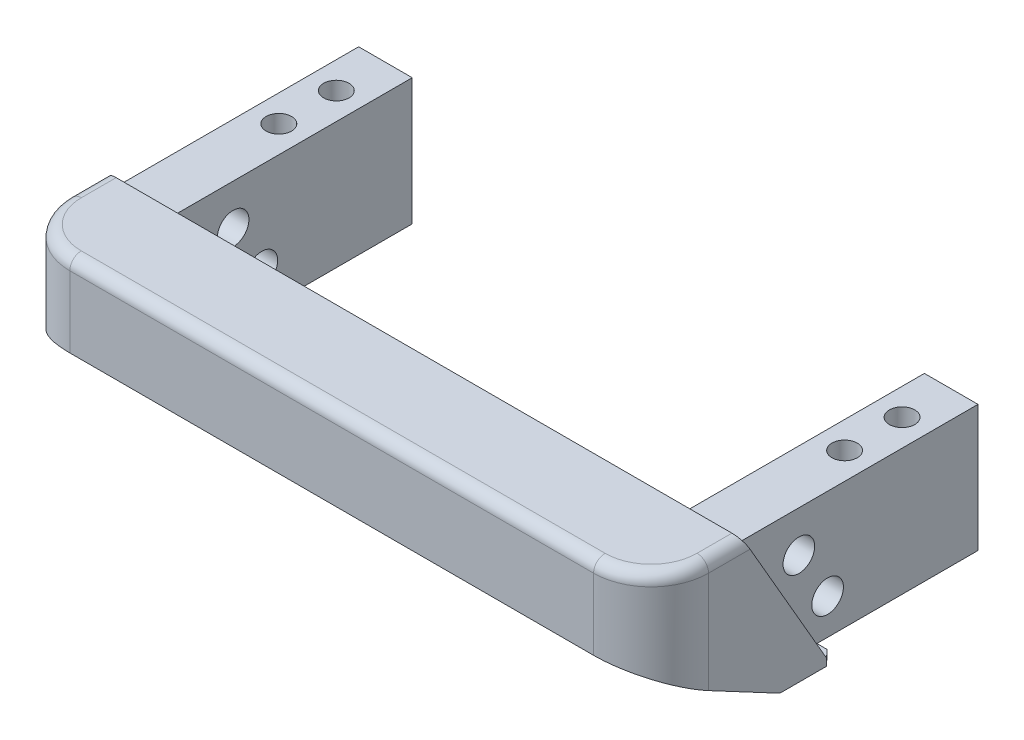
SolidWorks part; units mm, degrees
ref_plane "Front Plane" through (0, 0, 0) normal (0, 0, 1) x (1, 0, 0)
ref_plane "Top Plane" through (0, 0, 0) normal (0, 1, 0) x (1, 0, 0)
ref_plane "Right Plane" through (0, 0, 0) normal (1, 0, 0) x (0, 0, -1)
sketch "Sketch1" plane through (0, 0, 0) normal (1, 0, 0) x (0, 0, -1)
  line L0 (0, 0) -> (0, 50.8)
  line L5 (0, 50.8) -> (29.3294, 0)
  line L6 (29.3294, 0) -> (0, 0)
  dimension "D1" = 60
  dimension "D2" = 50.8
extrude "Boss-Extrude1" add sketch "Sketch1" along normal blind 222.25
sketch "Sketch3" plane through (0, 0, 0) normal (0, 0, 1) x (1, 0, 0)
  line L0 (196.85, 50.8) -> (196.85, 0) construction
  line L1 (218.875, 47.425) -> (200.225, 47.425)
  line L2 (218.875, 47.425) -> (218.875, 3.375)
  line L3 (218.875, 3.375) -> (200.225, 3.375)
  line L4 (200.225, 47.425) -> (200.225, 3.375)
  line L5 (222.25, 50.8) -> (222.25, 0) construction
  line L6 (222.25, 50.8) -> (0, 50.8) construction
  line L7 (222.25, 0) -> (0, 0) construction
  dimension "D1" = 3.375
  dimension "D2" = 3.375
  dimension "D3" = 3.375
  dimension "D4" = 18.65
  dimension "D5" = 25.4
extrude "Boss-Extrude3" add sketch "Sketch3" against normal blind 85 contours L1 L4 L3 L2 region at (209.55, 25.4, 0)
sketch "Sketch15" plane through (0, 47.425, 0) normal (0, 1, 0) x (1, 0, 0)
  circle A0 centre (209.55, 67.9086) radius 4.4196
  circle A1 centre (209.55, 47.9086) radius 4.4196
  dimension "D1" = 8.8392
  dimension "D2" = 8.8392
extrude "Cut-Extrude6" cut sketch "Sketch15" against normal blind 15
sketch "Sketch16" plane through (200.225, 0, 0) normal (-1, 0, 0) x (0, 0, 1)
  circle A0 centre (-22.6727, 33.1173) radius 5.5
  circle A1 centre (-32.6727, 15.7967) radius 5.5
  dimension "D1" = 11
  dimension "D2" = 11
extrude "Cut-Extrude7" cut sketch "Sketch16" against normal through all
ref_plane "Plane1" through (111.125, 0, 0) normal (-1, 0, 0) x (0, 0, 1)
mirror "Mirror1" about plane through (111.125, 0, 0) normal (-1, 0, 0) of "Cut-Extrude7", "Boss-Extrude3", "Cut-Extrude6"
sketch "Sketch4" plane through (222.25, 0, 0) normal (1, 0, 0) x (0, 0, -1)
  line L0 (-5, 50.8) -> (-26.1464, 36.606)
  line L3 (0, 0) -> (0, 50.8)
  line L4 (0, 50.8) -> (-5, 50.8)
  line L5 (0, 0) -> (-5, 0)
  line L6 (-15, 0) -> (-5, 0)
  line L7 (-5, 50.8) -> (-5, 0) construction
  arc A0 (-15, 0) -> (-26.1464, 36.606) centre (-15, 20) cw
  dimension "D2" = 20
  dimension "D1" = 10
  dimension "D3" = 5
extrude "Boss-Extrude4" [suppressed] add sketch "Sketch4" against normal up to surface (222.25 mm away) up to face at (0, 16.9333, -9.7765)
sketch "Sketch7" plane through (222.25, 0, 0) normal (1, 0, 0) x (0, 0, -1)
  line L0 (0, 50.8) -> (-32.1286, 50.8)
  line L2 (-32.1286, 22.0436) -> (9.3294, 0)
  line L3 (0, 0) -> (29.3294, 0) construction
  line L4 (9.3294, 0) -> (29.3294, 0)
  line L5 (29.3294, 0) -> (0, 50.8)
  line L8 (-32.1286, 50.8) -> (-32.1286, 22.0436)
  dimension "D1" = 32
  dimension "D2" = 20
  dimension "D3" = 32.1286
extrude "Boss-Extrude5" add sketch "Sketch7" against normal up to surface (222.25 mm away) up to face at (0, 16.9333, -9.7765)
sketch "Sketch8" plane through (222.25, 0, 0) normal (1, 0, 0) x (0, 0, -1)
  line L0 (-32.1286, 22.0436) -> (9.3294, 0) construction
  line L1 (0, 4.9605) -> (9.3294, 0)
  line L2 (0, 4.9605) -> (0, 0)
  line L3 (0, 0) -> (9.3294, 0)
extrude "Cut-Extrude3" cut sketch "Sketch8" against normal up to surface (222.25 mm away) up to face at (0, 21.434, 5.8213)
sketch "Sketch9" plane through (222.25, 0, 0) normal (1, 0, 0) x (0, 0, -1)
  line L0 (29.3294, 0) -> (73.6991, 0) construction
  line L1 (29.3294, 0) -> (29.4449, -0.2)
  line L2 (9.3294, 0) -> (12.6912, -1.7875)
  line L3 (-32.1286, 22.0436) -> (9.3294, 0) construction
  line L4 (29.3294, 0) -> (0, 50.8) construction
  line L5 (29.4449, -0.2) -> (32.5294, -0.2)
  line L6 (32.5294, -0.2) -> (32.5294, -1.7875)
  line L7 (32.5294, -1.7875) -> (12.6912, -1.7875)
  line L8 (9.3294, 0) -> (29.3294, 0) construction
  line L9 (9.3294, 0) -> (29.3294, 0)
  line M9 (9.3294, 0) -> (29.3294, 0)
  dimension "D1" = 0.2
  dimension "D2" = 1.5875
  dimension "D3" = 3.2
extrude "Boss-Extrude6" add sketch "Sketch9" against normal up to surface (222.25 mm away) contours L7 L6 L5 L1 L2 M9 region at (222.25, -0.8833, -21.595) up to face at (0, 24.7287, 5.1197)
sketch "Sketch10" plane through (0, -1.7875, 0) normal (0, -1, 0) x (1, 0, 0)
  line L0 (218.8722, -32.5294) -> (222.25, -28.8294)
  line L1 (0, -32.5294) -> (222.25, -32.5294) construction
  line L2 (222.25, -32.5294) -> (222.25, -12.6912) construction
  line L3 (222.25, -32.5294) -> (218.8722, -32.5294)
  line L4 (222.25, -32.5294) -> (222.25, -28.8294)
  line L6 (111.125, -32.5294) -> (197.8722, -32.5294)
  line L7 (111.125, -32.5294) -> (111.125, -29.4449)
  line L8 (111.125, -29.4449) -> (197.8722, -29.4449)
  line L9 (197.8722, -32.5294) -> (197.8722, -29.4449)
  line L10 (0, -9.2034) -> (222.25, -9.2034) construction
  line L11 (0, 32.1286) -> (0, -12.6912) construction
  line L12 (222.25, 32.1286) -> (222.25, -12.6912) construction
  line L13 (111.125, -9.2034) -> (111.125, -68.2914) construction
  line L14 (0, -29.4449) -> (222.25, -29.4449) construction
  dimension "D1" = 3.3778
  dimension "D2" = 3.7
  dimension "D3" = 21
extrude "Cut-Extrude4" cut sketch "Sketch10" against normal up to next
mirror "Mirror2" about plane through (111.125, 0, 0) normal (-1, 0, 0) of "Cut-Extrude4"
chamfer "Chamfer1" distance 3.5 angle 45 2 edges at (24.3778, -0.9937, -32.5294) (197.8722, -0.9937, -32.5294)
sketch "Sketch11" plane through (0, -1.7875, 0) normal (0, -1, 0) x (1, 0, 0)
  line L0 (111.125, -29.4449) -> (111.125, -11.1659) construction
  line L1 (198.2876, -29.4449) -> (23.9624, -29.4449) construction
  line L2 (0, -12.6912) -> (222.25, -12.6912) construction
  line L3 (66.125, -29.4449) -> (156.125, -29.4449)
  line L4 (66.125, -29.4449) -> (66.125, -12.6912)
  line L5 (66.125, -12.6912) -> (156.125, -12.6912)
  line L6 (156.125, -29.4449) -> (156.125, -12.6912)
  dimension "D1" = 90
extrude "Cut-Extrude5" cut sketch "Sketch11" against normal up to next
fillet "Fillet1" radius 4 1 edges at (111.125, -1.7875, -12.6912) tangent propagation no
fillet "Fillet2" radius 20 2 edges at (0, 36.4218, 32.1286) (222.25, 36.4218, 32.1286)
fillet "Fillet3" radius 4 5 edges at (0, 50.8, 6.0643) (5.8579, 50.8, 26.2708) (222.25, 50.8, 6.0643) (216.3921, 50.8, 26.2708) (111.125, 50.8, 32.1286)
equation "\"Length\"= 222.25"
equation "\"Height\"= 50.8"
equation "\"D2@Sketch1\"=\"Height\""
equation "\"D1@Boss-Extrude1\"=\"Length\""
equation "\"Slot\"= 3.175 + 0.2"
equation "\"D1@Sketch3\"=\"Slot\""
equation "\"D2@Sketch3\"=\"Slot\""
equation "\"D3@Sketch3\"=\"Slot\""
equation "\"Inside_Slot\"= 25.4 - ( 2 * 3.175 ) - ( 2 * 0.2 )"
equation "\"D4@Sketch3\"=\"Inside_Slot\""
